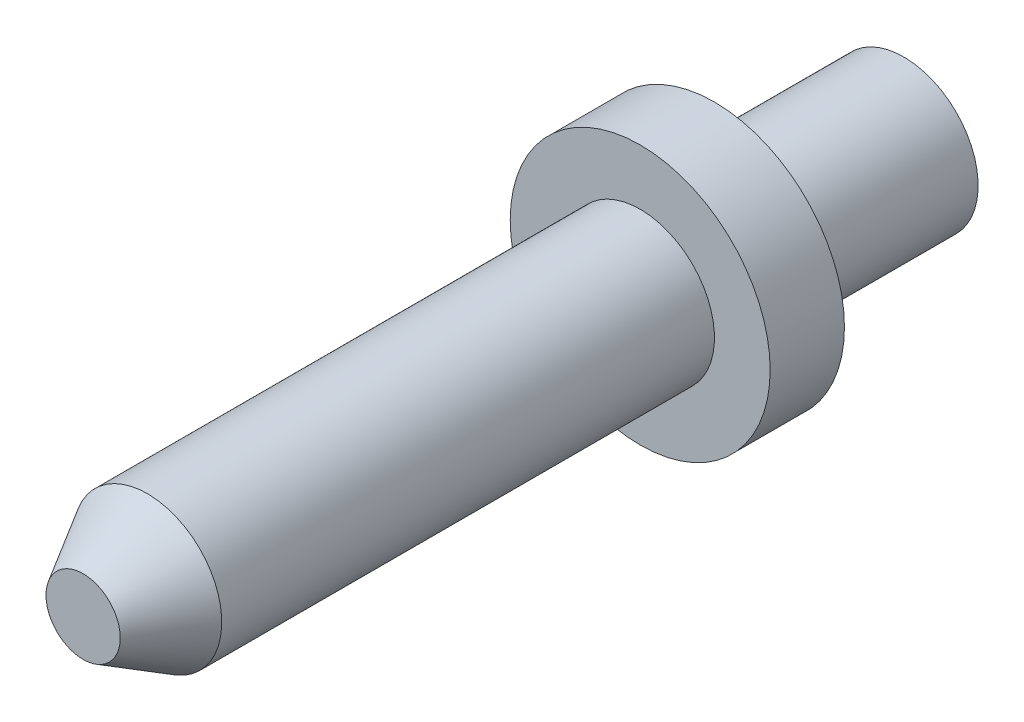
SolidWorks part; units mm, degrees
ref_plane "Front Plane" through (0, 0, 0) normal (0, 0, 1) x (1, 0, 0)
ref_plane "Top Plane" through (0, 0, 0) normal (0, 1, 0) x (1, 0, 0)
ref_plane "Right Plane" through (0, 0, 0) normal (1, 0, 0) x (0, 0, -1)
sketch "Sketch1" plane through (0, 0, 0) normal (0, 1, 0) x (1, 0, 0)
  line L0 (0, 1.7021) -> (0, -2.1079) construction
  line L1 (0, -2.1079) -> (0.508, -2.1079)
  line L3 (0, 1.7021) -> (0.508, 1.7021)
  line L4 (0.508, -2.1079) -> (0.508, 1.7021)
  line L5 (0, 0) -> (0.508, 1.7021) construction
  line L6 (0, 0) -> (0.508, -2.1079) construction
  line L7 (0.3175, 3.5055) -> (0.3175, 2.4895)
  line L8 (0, 1.7021) -> (0.889, 1.7021)
  line L9 (0, 1.7021) -> (0, 2.2101)
  line L10 (0, 2.2101) -> (0.889, 2.2101)
  line L11 (0.889, 1.7021) -> (0.889, 2.2101)
  line L12 (0, 2.2101) -> (0.508, 2.2101)
  line L13 (0, 2.2101) -> (0, 3.5055)
  line L14 (0, 3.5055) -> (0.508, 3.5055)
  line L15 (0.508, 2.2101) -> (0.508, 3.5055)
  line L16 (0.3175, 2.4895) -> (0, 2.3207)
  line L17 (0.508, -1.6679) -> (0.254, -2.1079)
  line L18 (0, 1.7021) -> (0, -2.1079)
  point P0 (0, 0)
  dimension "D1" = 3.81
  dimension "D2" = 0.508
  dimension "D3" = 0.508
  dimension "D4" = 118
  dimension "D5" = 0.3175
  dimension "D6" = 0.889
  dimension "D7" = 0.508
  dimension "D8" = 1.2954
  dimension "D9" = 1.016
  dimension "D10" = 60
  dimension "D11" = 0.254
revolve "Revolve1" add sketch "Sketch1" angle 360 about L18 region at (0.249, 0, 0.1506) region at (0.4445, 0, -1.9561) region at (0.3664, 0, -2.7487)
